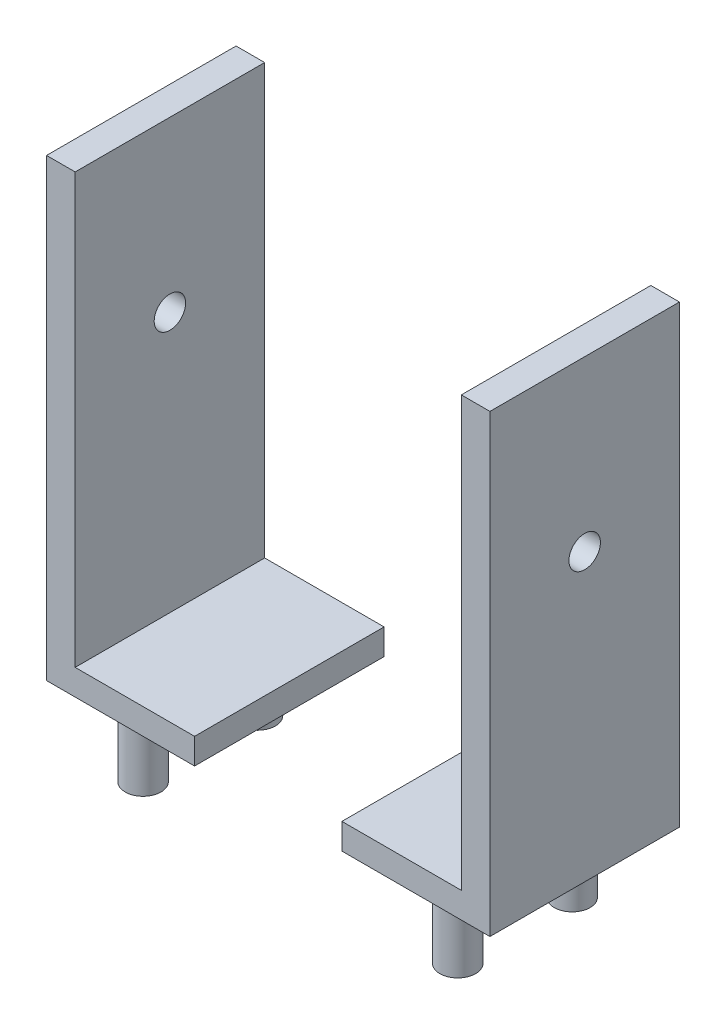
SolidWorks part; units mm, degrees
ref_plane "Front Plane" through (0, 0, 0) normal (0, 0, 1) x (1, 0, 0)
ref_plane "Top Plane" through (0, 0, 0) normal (0, 1, 0) x (1, 0, 0)
ref_plane "Right Plane" through (0, 0, 0) normal (1, 0, 0) x (0, 0, -1)
sketch "Sketch1" plane through (0, 0, 0) normal (0, 1, 0) x (1, 0, 0)
  line L0 (0, 6.25) -> (31, 6.25) construction
  line L5 (0, 0) -> (31, 0)
  line L6 (0, 0) -> (0, 13.25)
  line L7 (0, 13.25) -> (31, 13.25)
  line L8 (31, 0) -> (31, 13.25)
  circle A0 centre (4.5, 2.25) radius 1.25
  circle A1 centre (26.5, 2.25) radius 1.25
  circle A2 centre (26.5, 10.25) radius 1.25
  circle A3 centre (4.5, 10.25) radius 1.25
  dimension "D3" = 2.5
  dimension "D4" = 2.5
  dimension "D5" = 22
  dimension "D1" = 4.5
  dimension "D2" = 4.5
  dimension "D6" = 2.25
  dimension "D7" = 4
  dimension "D8" = 3
extrude "Boss-Extrude1" add sketch "Sketch1" along normal blind 1.8
sketch "Sketch2" plane through (0, 1.8, 0) normal (0, 1, 0) x (1, 0, 0)
  line L1 (0, 13.25) -> (2, 13.25)
  line L2 (0, 13.25) -> (0, 0)
  line L3 (0, 0) -> (2, 0)
  line L4 (2, 13.25) -> (2, 0)
  line L5 (15.5, 13.25) -> (15.5, 0) construction
  line L6 (29, 13.25) -> (31, 13.25)
  line L7 (29, 13.25) -> (29, 0)
  line L8 (29, 0) -> (31, 0)
  line L9 (31, 13.25) -> (31, 0)
  line L10 (31, 13.25) -> (0, 13.25) construction
  line L11 (0, 0) -> (31, 0) construction
  point P14 (0, 0)
  point P15 (0, 0)
  point P16 (0, 0)
  point P17 (0, 0)
  point P18 (0, 0)
  dimension "D1" = 13.5
  dimension "D2" = 2
  dimension "D4" = 27
  dimension "D5" = 2
  dimension "D7" = 13.5
sketch "Sketch4" plane through (0, 0, 0) normal (0, -1, 0) x (1, 0, 0)
  circle A0 centre (4.5, -2.25) radius 1.25
  circle A1 centre (26.5, -2.25) radius 1.25
  circle A2 centre (26.5, -10.25) radius 1.25
  circle A3 centre (4.5, -10.25) radius 1.25
extrude "Boss-Extrude2" add sketch "Sketch4" along normal blind 5 separate body
extrude "Boss-Extrude4" add sketch "Sketch4<4>" against normal blind 1.8
sketch "Sketch4<4>" plane through (0, 0, 0) normal (0, -1, 0) x (1, 0, 0) same geometry as "Sketch4"
extrude "Boss-Extrude5" add sketch "Sketch2" along normal blind 30
sketch "Sketch6" plane through (0, 1.8, 0) normal (0, 1, 0) x (1, 0, 0)
  line L0 (29, 13.25) -> (2, 13.25) construction
  line L1 (2, 0) -> (2, 13.25) construction
  line L2 (2, 0) -> (29, 0) construction
  line L3 (10.3492, 13.25) -> (20.6508, 13.25)
  line L4 (10.3492, 13.25) -> (10.3492, 0)
  line L5 (10.3492, 0) -> (20.6508, 0)
  line L6 (20.6508, 13.25) -> (20.6508, 0)
  point P2 (15.5, 13.25)
  point P11 (15.5, 13.25)
  dimension "D1" = 13.5
extrude "Cut-Extrude1" cut sketch "Sketch6" against normal up to surface (1.8 mm away) up to face at (4.5, 0, -11.5)
sketch "Sketch7" plane through (31, 0, 0) normal (1, 0, 0) x (0, 0, -1)
  line L0 (0, 0) -> (13.25, 0) construction
  line L3 (0, 31.8) -> (13.25, 31.8) construction
  circle A0 centre (6.625, 20) radius 1.1
  point P10 (6.625, 31.8)
  dimension "D1" = 2.2
  dimension "D2" = 20
extrude "Cut-Extrude2" cut sketch "Sketch7" against normal up to surface (31 mm away) up to face at (0, 15.9, -6.625)
